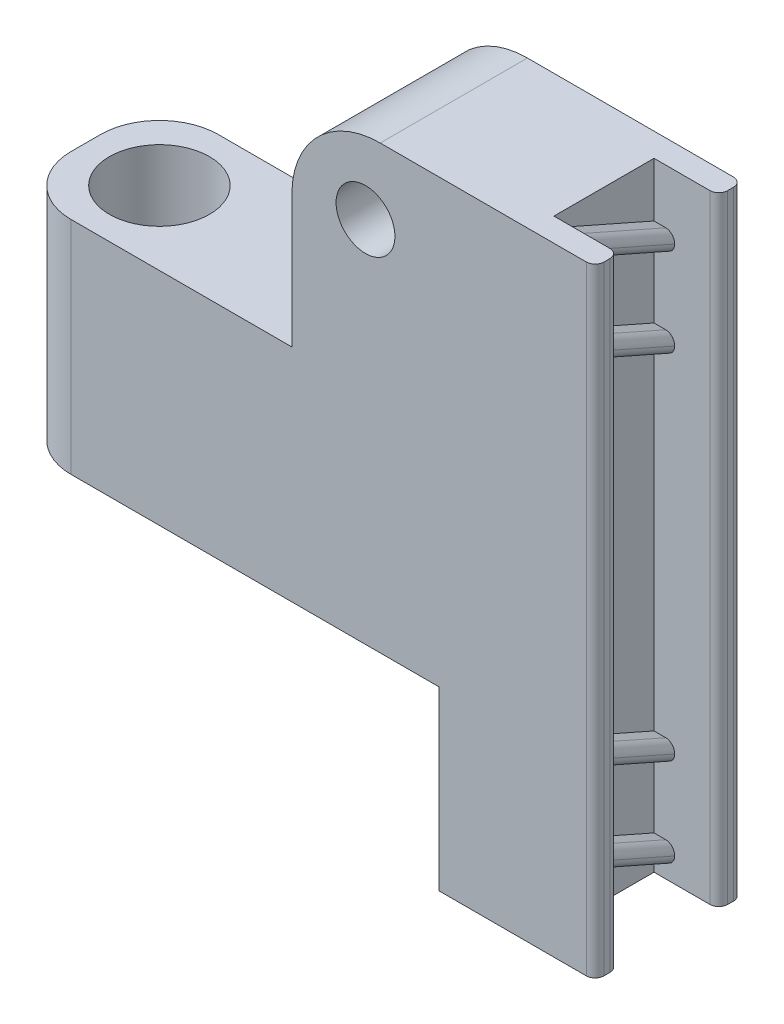
SolidWorks part; units mm, degrees
ref_plane "前基準面" through (0, 0, 0) normal (0, 0, 1) x (1, 0, 0)
ref_plane "上基準面" through (0, 0, 0) normal (0, 1, 0) x (1, 0, 0)
ref_plane "右基準面" through (0, 0, 0) normal (1, 0, 0) x (0, 0, -1)
sketch "草圖1" plane through (0, 0, 0) normal (0, 1, 0) x (1, 0, 0)
  line L0 (17.3, -0.8) -> (14.5, -0.8)
  line L1 (0, 0) -> (17.3, 0)
  line L3 (0, -5) -> (17.3, -5)
  line L4 (17.3, 0) -> (17.3, -0.8)
  line L5 (14.5, -0.8) -> (14.5, -4.2)
  line L6 (14.5, -4.2) -> (17.3, -4.2)
  line L7 (17.3, -4.2) -> (17.3, -5)
  line L9 (0, 0) -> (0, -5) construction
  line L10 (0, 0) -> (-2.5, 0)
  line L11 (-2.5, 0) -> (-2.5, -5)
  line L12 (-2.5, -5) -> (0, -5)
  circle A1 centre (0, -2.5) radius 1.7
  dimension "D2" = 2.5
  dimension "D7" = 3.4
  dimension "D1" = 5
  dimension "D3" = 17.3
  dimension "D4" = 0.8
  dimension "D5" = 0.8
  dimension "D6" = 14.5
extrude "填料-伸長1" add sketch "草圖1" along normal blind 21
sketch "草圖2" plane through (14.5, 0, 0) normal (1, 0, 0) x (0, 0, -1)
  line L0 (-4.2, 5.6558) -> (-0.8, 4.1558)
  line L2 (-0.8, 21) -> (-0.8, 0) construction
  line L3 (-0.8, 4.1558) -> (-0.8, 3.5)
  line L5 (-0.8, 3.5) -> (-4.2, 5)
  line L6 (-4.2, 5) -> (-4.2, 5.6558)
  line L7 (-4.2, 2.6558) -> (-0.8, 1.1558)
  line L8 (-4.2, 21) -> (-4.2, 0) construction
  line L9 (-0.8, 1.1558) -> (-0.8, 0.5)
  line L10 (-0.8, 0.5) -> (-4.2, 2)
  line L11 (-4.2, 2) -> (-4.2, 2.6558)
  line L24 (-4.2, 17.6558) -> (-0.8, 16.1558)
  line L25 (-0.8, 16.1558) -> (-0.8, 15.5)
  line L26 (-0.8, 15.5) -> (-4.2, 17)
  line L27 (-4.2, 17) -> (-4.2, 17.6558)
  line L28 (-4.2, 20.6558) -> (-0.8, 19.1558)
  line L29 (-0.8, 19.1558) -> (-0.8, 18.5)
  line L30 (-0.8, 18.5) -> (-4.2, 20)
  line L31 (-4.2, 20) -> (-4.2, 20.6558)
  line L32 (-4.2, 14.6558) -> (-0.8, 13.1558) [skipped]
  line L33 (-0.8, 13.1558) -> (-0.8, 12.5) [skipped]
  line L34 (-0.8, 12.5) -> (-4.2, 14) [skipped]
  line L35 (-4.2, 14) -> (-4.2, 14.6558) [skipped]
  line L36 (-4.2, 8.6558) -> (-0.8, 7.1558) [skipped]
  line L37 (-0.8, 7.1558) -> (-0.8, 6.5) [skipped]
  line L38 (-0.8, 6.5) -> (-4.2, 8) [skipped]
  line L39 (-4.2, 8) -> (-4.2, 8.6558) [skipped]
  line L40 (-4.2, 11.6558) -> (-0.8, 10.1558) [skipped]
  line L41 (-0.8, 10.1558) -> (-0.8, 9.5) [skipped]
  line L42 (-0.8, 9.5) -> (-4.2, 11) [skipped]
  line L43 (-4.2, 11) -> (-4.2, 11.6558) [skipped]
  dimension "D1" = 0.6
  dimension "D2" = 7
  dimension "D4" = 0.5
  dimension "D5" = 1.5
extrude "填料-伸長2" add sketch "草圖2" along normal blind 1.3
fillet "圓角1" radius 0.3 8 edges at (15.8, 1.9058, 2.5) (15.8, 1.25, 2.5) (15.8, 4.25, 2.5) (15.8, 4.9058, 2.5) (15.8, 16.25, 2.5) (15.8, 16.9058, 2.5) (15.8, 19.25, 2.5) (15.8, 19.9058, 2.5)
fillet "圓角2" radius 0.3 4 edges at (17.3, 10.5, 5) (17.3, 10.5, 0) (17.3, 10.5, 0.8) (17.3, 10.5, 4.2)
sketch "草圖3" plane through (0, 0, 0) normal (0, 0, 1) x (1, 0, 0)
  line L0 (-2.5, 21) -> (17, 21) construction
  line L2 (-2.5, 21) -> (-2.5, 0) construction
  circle A1 centre (9.5, 18.5) radius 1
  dimension "D4" = 2
  dimension "D1" = 2.5
  dimension "D2" = 12
extrude "除料-伸長3" cut sketch "草圖3" along normal blind 10
fillet "圓角3" radius 2 2 edges at (-2.5, 10.5, 5) (-2.5, 10.5, 0)
sketch "草圖4" plane through (14.5, 0, 0) normal (1, 0, 0) x (0, 0, -1)
  line L1 (-4.2, 21) -> (-0.8, 21)
  line L2 (-4.2, 21) -> (-4.2, 0)
  line L3 (-4.2, 0) -> (-0.8, 0)
  line L4 (-0.8, 21) -> (-0.8, 0)
extrude "填料-伸長4" add sketch "草圖4" along normal blind 0.6
ref_axis "基準軸1" through (0, 21, 2.5) along (0, -1, 0)
sketch "草圖5" plane through (0, 0, 0) normal (0, 0, 1) x (1, 0, 0)
  line L0 (12, 13.7707) -> (12, -0.7532) construction
  line L1 (0, 21) -> (0, 0) construction
  dimension "D1" = 12
sketch "草圖6" plane through (0, 21, 0) normal (0, 1, 0) x (1, 0, 0)
  line L0 (0, -2.5) -> (16.7, -2.5) construction
  line L2 (14.499, -0.1435) -> (16, -0.1435)
  line L3 (16, -0.1435) -> (16, -0.6265)
  line L4 (16, -4.3735) -> (16, -4.6222)
  line L5 (14.499, -0.1435) -> (14.499, -4.6222)
  line L6 (14.499, -4.6222) -> (16, -4.6222)
  line L7 (15.1, -0.8) -> (15.1, -4.2) construction
  arc A0 (16, -0.6265) -> (16, -4.3735) centre (16.7, -2.5) ccw
  dimension "D2" = 0.9
  dimension "D1" = 2
sketch "草圖7" plane through (0, 0, 5) normal (0, 0, 1) x (1, 0, 0)
  line L0 (0, 21) -> (0, 0) construction
  line L1 (-3, 6) -> (12, 6)
  line L2 (-3, 6) -> (-3, -7.5365)
  line L3 (-3, -7.5365) -> (12, -7.5365)
  line L4 (12, 6) -> (12, -7.5365)
  line L5 (-0.5, 21) -> (17, 21) construction
  line L6 (-0.5, 21) -> (17, 21) construction
  line L7 (-3, 23) -> (7, 23)
  line L8 (-3, 23) -> (-3, 13.5)
  line L9 (-3, 13.5) -> (7, 13.5)
  line L10 (7, 23) -> (7, 13.5)
  circle A0 centre (9.5, 18.5) radius 1 construction
  dimension "D4" = 2.5
  dimension "D1" = 12
  dimension "D2" = 15
  dimension "D3" = 15
  dimension "D5" = 2
  dimension "D6" = 7.5
extrude "除料-伸長4" cut sketch "草圖7" against normal blind 10
fillet "圓角7" radius 3 1 edges at (7, 21, 2.5)
